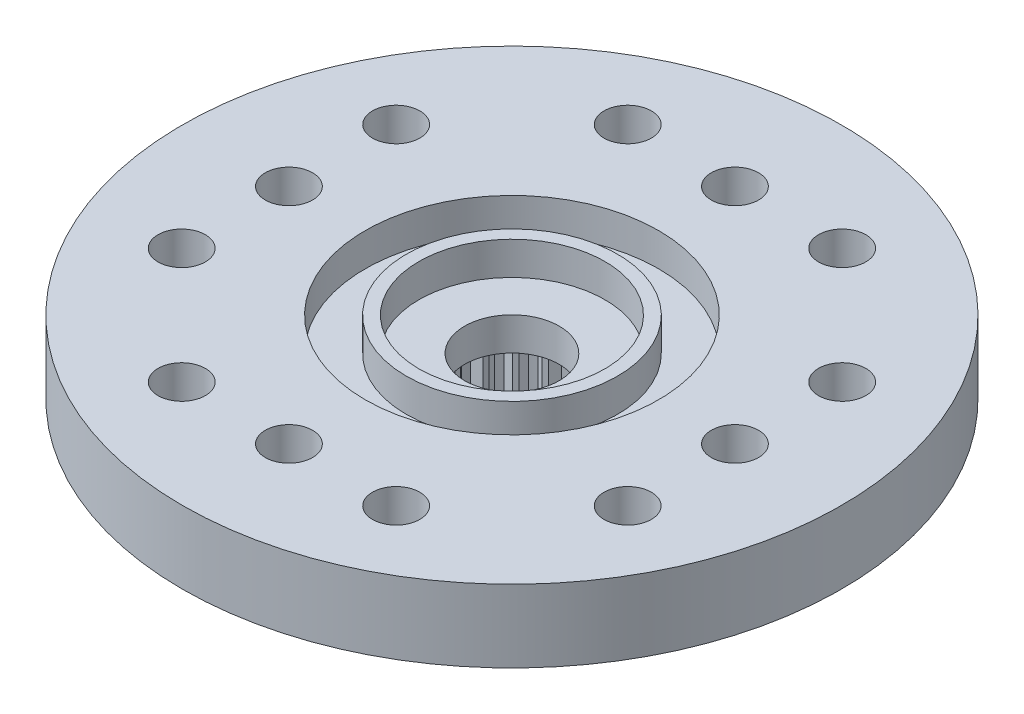
SolidWorks part; units mm, degrees
material "PA Type 6"
ref_plane "Plan de face" through (0, 0, 0) normal (0, 0, 1) x (1, 0, 0)
ref_plane "Plan de dessus" through (0, 0, 0) normal (0, 1, 0) x (1, 0, 0)
ref_plane "Plan de droite" through (0, 0, 0) normal (1, 0, 0) x (0, 0, -1)
ref_axis "Axe1" through (0, 0, 0) along (0, 1, 0)
sketch "Esquisse1" plane through (0, 0, 0) normal (0, 1, 0) x (1, 0, 0)
  line L0 (-10.45, 0) -> (10.45, 0) construction
  line L1 (0, 0) -> (0, -8.9896) construction
  line L4 (-7.0711, 7.0711) -> (-7.0711, -7.0711) construction
  line L5 (-7.0711, -7.0711) -> (7.0711, 7.0711) construction
  line L6 (-7.0711, -7.0711) -> (7.0711, -7.0711) construction
  line L7 (7.0711, -7.0711) -> (7.0711, 7.0711) construction
  line L8 (-7.0711, 7.0711) -> (7.0711, 7.0711) construction
  line L9 (0, -7.0711) -> (0, 7.0711) construction
  line L10 (-7.0711, 0) -> (7.0711, 0) construction
  line L11 (-7.0711, 7.0711) -> (7.0711, -7.0711) construction
  circle A0 centre (0, 0) radius 10.45 construction
  circle A1 centre (0, 0) radius 6.075
  circle A7 centre (3.4, -7.0711) radius 0.75
  circle A8 centre (0, -7.0711) radius 0.75
  circle A9 centre (-3.4, -7.0711) radius 0.75
  circle A10 centre (0, 0) radius 7.0711 construction
  circle A11 centre (7.0711, -3.4) radius 0.75
  circle A12 centre (0, 0) radius 4.65
  circle A13 centre (0, 0) radius 1.5
  circle A14 centre (0, 0) radius 3.35
  circle A15 centre (0, 0) radius 2.95
  circle A16 centre (7.0711, 0) radius 0.75
  circle A17 centre (-7.0711, 3.4) radius 0.75
  circle A18 centre (-7.0711, -3.4) radius 0.75
  circle A19 centre (7.0711, 3.4) radius 0.75
  circle A20 centre (-3.4, 7.0711) radius 0.75
  circle A21 centre (-7.0711, 0) radius 0.75
  circle A22 centre (0, 7.0711) radius 0.75
  circle A23 centre (3.4, 7.0711) radius 0.75
  circle A24 centre (0, 0) radius 7.846 construction
  dimension "D1" = 20.9
  dimension "D2" = 12.15
  dimension "D3" = 20
  dimension "D9" = 9.3
  dimension "D10" = 6.7
  dimension "D11" = 0.4
  dimension "D12" = 3
  dimension "D4" = 1.5
  dimension "D5" = 6.8
sketch "Esquisse2" plane through (0, 0, 0) normal (0, 0, 1) x (1, 0, 0)
  line L0 (0, 3.9296) -> (0, -5.2174) construction
  line L1 (21.01, 0) -> (-21.01, 0) construction
  line L2 (0, -3.5) -> (-4.45, -3.5)
  line L3 (0, -3.5) -> (0, 2.1)
  line L4 (0, 2.1) -> (-4.45, 2.1)
  line L5 (-4.45, -3.5) -> (-4.45, 2.1)
  point P9 (-4.45, -0.2)
  dimension "D1" = 8.9
  dimension "D2" = 3.5
  dimension "D3" = 3.3
  dimension "D4" = 2.3
revolve "Révolution1" add sketch "Esquisse2" angle 360 about L0
sketch "Esquisse3" plane through (0, 2.1, 0) normal (0, 1, 0) x (1, 0, 0)
  line L4 (0, 0) -> (0, -8.9896) construction
  line L5 (0, 0) -> (0, -8.9896) construction
  circle A6 centre (0, 0) radius 10.45
  circle A7 centre (0, 0) radius 10.45 construction
  circle A20 centre (-3.4, 7.0711) radius 0.75 construction
  circle A21 centre (-3.4, 7.0711) radius 0.75
  circle A22 centre (0, 7.0711) radius 0.75 construction
  circle A23 centre (0, 7.0711) radius 0.75
  circle A24 centre (3.4, 7.0711) radius 0.75 construction
  circle A25 centre (3.4, 7.0711) radius 0.75
  circle A26 centre (-7.0711, 3.4) radius 0.75 construction
  circle A27 centre (-7.0711, 0) radius 0.75 construction
  circle A28 centre (-7.0711, -3.4) radius 0.75 construction
  circle A29 centre (-3.4, -7.0711) radius 0.75 construction
  circle A30 centre (0, -7.0711) radius 0.75 construction
  circle A31 centre (3.4, -7.0711) radius 0.75 construction
  circle A32 centre (-7.0711, 3.4) radius 0.75
  circle A33 centre (-7.0711, 0) radius 0.75
  circle A34 centre (-7.0711, -3.4) radius 0.75
  circle A35 centre (-3.4, -7.0711) radius 0.75
  circle A36 centre (0, -7.0711) radius 0.75
  circle A37 centre (3.4, -7.0711) radius 0.75
  circle A38 centre (7.0711, 3.4) radius 0.75 construction
  circle A39 centre (7.0711, 0) radius 0.75 construction
  circle A40 centre (7.0711, -3.4) radius 0.75 construction
  circle A41 centre (7.0711, 3.4) radius 0.75
  circle A42 centre (7.0711, 0) radius 0.75
  circle A43 centre (7.0711, -3.4) radius 0.75
extrude "Boss.-Extru.1" add sketch "Esquisse3" against normal up to vertex (2.3 mm away) up to point (-4.45, -0.2, 0)
sketch "Esquisse4" plane through (0, 2.1, 0) normal (0, 1, 0) x (1, 0, 0)
  circle A0 centre (0, 0) radius 2.95 construction
  circle A1 centre (0, 0) radius 2.95
extrude "Enlèv. mat.-Extru.1" cut sketch "Esquisse4" against normal blind 1.05
sketch "Esquisse5" plane through (0, 2.1, 0) normal (0, 1, 0) x (1, 0, 0)
  circle A0 centre (0, 0) radius 3.35 construction
  circle A1 centre (0, 0) radius 4.65 construction
  circle A2 centre (0, 0) radius 3.35
  circle A3 centre (0, 0) radius 4.65
extrude "Enlèv. mat.-Extru.2" cut sketch "Esquisse5" against normal blind 1.05
sketch "Esquisse6" plane through (0, -3.5, 0) normal (0, -1, 0) x (1, 0, 0)
  circle A0 centre (0, 0) radius 1.5 construction
  circle A1 centre (0, 0) radius 1.5
extrude "Enlèv. mat.-Extru.3" cut sketch "Esquisse6" against normal through all
sketch "Esquisse7" plane through (0, 0, 0) normal (0, 1, 0) x (1, 0, 0)
  line L6 (0.1267, -2.9973) -> (0.2711, -2.6537)
  line L7 (0.3973, -2.6377) -> (0.6227, -2.9347)
  line L8 (0, 0) -> (0, -3.7146) construction
  line L9 (0, 0) -> (0.3388, -2.6821) construction
  arc A4 (0.1267, -2.9973) -> (0.6227, -2.9347) centre (0, 0) ccw
  arc A5 (0.3973, -2.6377) -> (0.2711, -2.6537) centre (0.3388, -2.6821) ccw
  dimension "D2" = 6
  dimension "D7" = 0.37
  dimension "D4" = 0.5
  dimension "D5" = 7.2
  dimension "D6" = 60
sketch "Esquisse8" plane through (0, 0, 0) normal (0, 1, 0) x (1, 0, 0)
  circle A0 centre (0, 0) radius 2.68
  arc A1 (0.3973, -2.6377) -> (0.2711, -2.6537) centre (0.3388, -2.6821) ccw construction
  dimension "D1" = 0.05
extrude "Enlèv. mat.-Extru.4" cut sketch "Esquisse8" against normal through all
sketch "Esquisse9" plane through (0, 0, 0) normal (0, 1, 0) x (1, 0, 0)
  line L0 (0.1267, -2.9973) -> (0.2711, -2.6537) construction
  line L2 (0.1053, -3.0482) -> (0.2656, -2.6668)
  line L3 (-0.2656, -2.6668) -> (-0.1053, -3.0482)
  line L4 (0, -2.4923) -> (0, -2.738) construction
  line L5 (0, 0) -> (0, -3.7146) construction
  arc A0 (-0.1053, -3.0482) -> (0.1053, -3.0482) centre (0, 0) ccw
  circle A1 centre (0, 0) radius 2.68
  arc A2 (-0.2656, -2.6668) -> (0.2656, -2.6668) centre (0, 0) ccw
  arc A3 (0.1267, -2.9973) -> (0.6227, -2.9347) centre (0, 0) ccw construction
  dimension "D2" = 0.05
  dimension "D1" = 0
extrude "Enlèv. mat.-Extru.5" cut sketch "Esquisse9" against normal through all
pattern_circular "Répétition circulaire1" count 25 over 360 about axis through (0, 0, 0) along (0, 1, 0) of "Enlèv. mat.-Extru.5"
